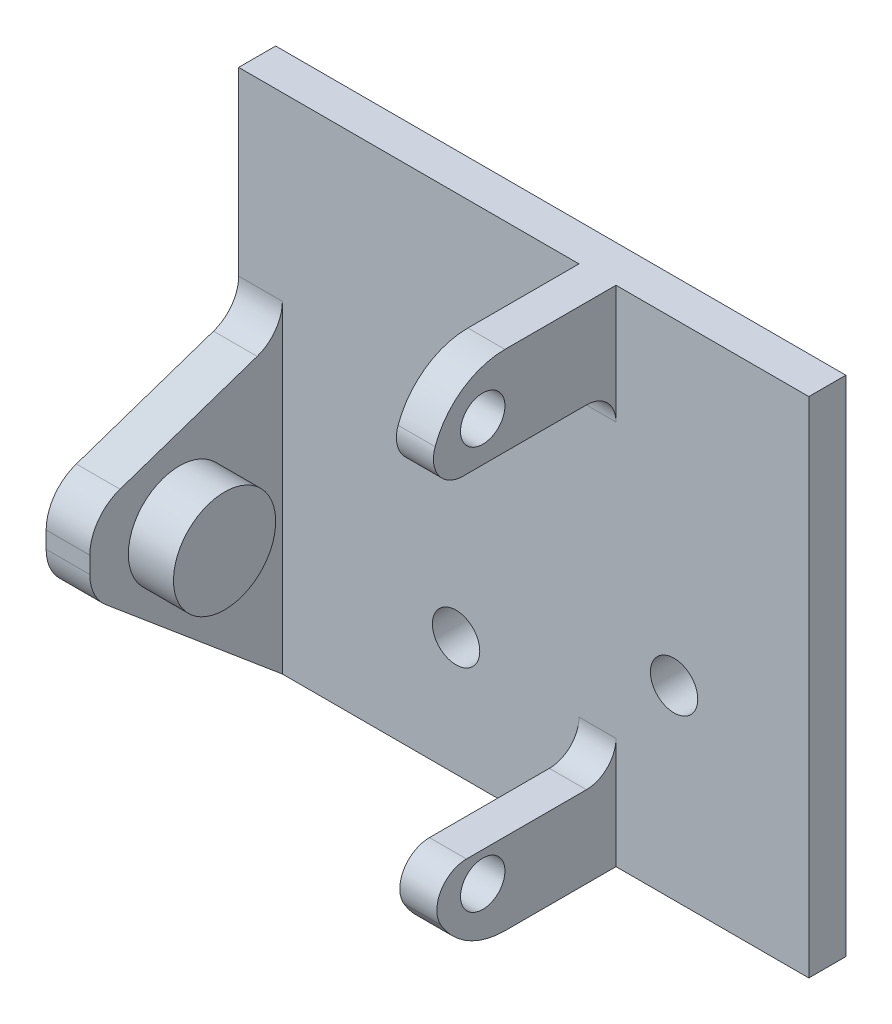
SolidWorks part; units mm, degrees
ref_plane "Plano frontal" through (0, 0, 0) normal (0, 0, 1) x (1, 0, 0)
ref_plane "Plano superior" through (0, 0, 0) normal (0, 1, 0) x (1, 0, 0)
ref_plane "Plano direito" through (0, 0, 0) normal (1, 0, 0) x (0, 0, -1)
sketch "Esboço1" plane through (0, 0, 0) normal (0, 0, 1) x (1, 0, 0)
  line L1 (-22.645, 6.7101) -> (15.855, 6.7101)
  line L2 (-22.645, 6.7101) -> (-22.645, -27.2899)
  line L3 (-22.645, -27.2899) -> (15.855, -27.2899)
  line L4 (15.855, 6.7101) -> (15.855, -27.2899)
  dimension "D1" = 38.5
  dimension "D2" = 34
extrude "Ressalto-extrusão1" add sketch "Esboço1" along normal blind 2.5
sketch "Esboço2" plane through (0, 0, 2.5) normal (0, 0, 1) x (1, 0, 0)
  line L0 (1.585, 6.7101) -> (1.585, -27.2899) construction
  line L1 (15.855, 6.7101) -> (-22.645, 6.7101) construction
  line L3 (0.335, 6.7101) -> (0.335, 0.7101)
  line L4 (0.335, 0.7101) -> (2.835, 0.7101)
  line L5 (2.835, 6.7101) -> (2.835, 0.7101)
  line L6 (0.335, 6.7101) -> (2.835, 6.7101)
  line L7 (-22.645, -21.7899) -> (15.855, -21.7899) construction
  line L8 (-22.645, 6.7101) -> (-22.645, -27.2899) construction
  line L9 (15.855, -27.2899) -> (15.855, 6.7101) construction
  line L28 (0.335, 6.7101) -> (0.335, -27.2899) construction
  line L29 (-22.645, -27.2899) -> (15.855, -27.2899) construction
  line L30 (2.835, 6.7101) -> (2.835, -27.2899) construction
  line L31 (0.335, -27.2899) -> (0.335, -21.7899)
  line L32 (0.335, -21.7899) -> (2.835, -21.7899)
  line L33 (2.835, -21.7899) -> (2.835, -27.2899)
  line L34 (2.835, -27.2899) -> (0.335, -27.2899)
  point P11 (1.585, 0.7101)
  dimension "D1" = 1.25
  dimension "D2" = 22.5
  dimension "D3" = 6
  dimension "D4" = 24.23
  dimension "D5" = 14.27
extrude "Ressalto-extrusão2" add sketch "Esboço2" along normal blind 12.5
sketch "Esboço3" plane through (2.835, 0, 0) normal (1, 0, 0) x (0, 0, -1)
  line L0 (-11.5, 6.7101) -> (-11.5, 0.7101) construction
  line L1 (-15, 6.7101) -> (-2.5, 6.7101) construction
  line L2 (-15, 0.7101) -> (-2.5, 0.7101) construction
  line L3 (-2.5, 0.7101) -> (-2.5, 6.7101) construction
  line L4 (-11.5, 6.7101) -> (-11.5, -27.2899) construction
  line L5 (-15, -21.7899) -> (-2.5, -21.7899) construction
  circle A0 centre (-11.5, 3.4101) radius 1.5
  circle A1 centre (-11.5, -23.7899) radius 1.5
  point P10 (-11.5, 1.9101)
  point P16 (-11.5, -25.2899)
  point P17 (-11.5, -22.2899)
  dimension "D2" = 1.2
  dimension "D3" = 2
  dimension "D1" = 9
extrude "Corte-extrusão1" cut sketch "Esboço3" against normal up to next
sketch "Esboço4" plane through (0, 0, 2.5) normal (0, 0, 1) x (1, 0, 0)
  line L0 (-19.695, 6.7101) -> (-19.695, -27.2899) construction
  line L1 (0.335, 6.7101) -> (-22.645, 6.7101) construction
  line L2 (-22.645, -27.2899) -> (0.335, -27.2899) construction
  line L3 (-22.645, 6.7101) -> (-22.645, -27.2899) construction
  line L4 (-19.695, -27.2899) -> (-19.695, -7.2899)
  line L5 (-19.695, -7.2899) -> (-22.645, -7.2899)
  line L6 (-22.645, -7.2899) -> (-22.645, -27.2899)
  line L7 (-22.645, -27.2899) -> (-19.695, -27.2899)
  point P6 (-19.695, -7.2899)
  dimension "D1" = 2.95
  dimension "D2" = 20
extrude "Ressalto-extrusão3" add sketch "Esboço4" along normal blind 13
sketch "Esboço5" plane through (-22.645, 0, 0) normal (-1, 0, 0) x (0, 0, 1)
  line L0 (2.5, -7.2899) -> (2.5, -27.2899) construction
  line L1 (2.5, -15.0899) -> (15.5, -15.0899) construction
  line L2 (15.5, -7.2899) -> (15.5, -27.2899) construction
  line L3 (15.5, -27.2899) -> (0, -27.2899) construction
  line L4 (2.5, -27.2899) -> (15.5, -16.3664)
  line L6 (15.5, -11.6895) -> (2.5, -7.2899)
  line L7 (15.222, -11.5954) -> (15.222, -16.5999)
  circle A0 centre (9.45, -15.0899) radius 3.45
  line M3 (0, -27.2899) -> (15.5, -27.2899)
  line M4 (15.5, -27.2899) -> (15.5, -7.2899)
  line M5 (15.5, -7.2899) -> (2.5, -7.2899)
  dimension "D2" = 6.95
  dimension "D1" = 12.2
extrude "Corte-extrusão2" cut sketch "Esboço5" against normal blind 15 contours L6 M4 M5 | L4 M3 M4 | A0 region at (-22.645, -23.6487, 11.1667) region at (-22.645, -8.7564, 11.1667) region at (-22.645, -15.0899, 9.45)
fillet "Filete1" radius 3 2 edges at (-21.17, -16.3664, 15.5) (-21.17, -11.6895, 15.5)
fillet "Filete2" radius 2.5 1 edges at (-21.17, -7.2899, 2.5)
sketch "Esboço6" plane through (-19.695, 0, 0) normal (1, 0, 0) x (0, 0, -1)
  circle A0 centre (-9.45, -15.0899) radius 3.45
sketch "Esboço7" plane through (-22.645, 0, 0) normal (-1, 0, 0) x (0, 0, 1)
  circle A0 centre (9.45, -15.0899) radius 3.45
extrude "Ressalto-extrusão5" add sketch "Esboço7" against normal blind 6
sketch "Esboço8" plane through (0, 0, 0) normal (0, 0, -1) x (-1, 0, 0)
  line L0 (7.965, 6.7101) -> (7.965, -27.2899) construction
  line L1 (-15.855, 6.7101) -> (22.645, 6.7101) construction
  line L2 (22.645, -27.2899) -> (-15.855, -27.2899) construction
  line L3 (22.645, 6.7101) -> (22.645, -27.2899) construction
  line L4 (7.965, -19.2899) -> (22.645, -19.2899) construction
  line L6 (-6.755, 6.7101) -> (-6.755, -27.2899) construction
  line L7 (-15.855, -27.2899) -> (-15.855, 6.7101) construction
  line L8 (-15.855, -14.7399) -> (-6.755, -14.7399) construction
  circle A1 centre (7.965, -19.2899) radius 1.6
  circle A2 centre (-6.755, -14.7399) radius 1.6
  dimension "D3" = 3.2
  dimension "D4" = 9.1
  dimension "D6" = 3.2
  dimension "D1" = 14.68
  dimension "D2" = 8
  dimension "D5" = 12.55
extrude "Corte-extrusão3" cut sketch "Esboço8" against normal blind 6
fillet "Filete3" radius 2 2 edges at (1.585, -21.7899, 2.5) (1.585, 0.7101, 2.5)
fillet "Filete4" radius 5 2 edges at (1.585, -27.2899, 15) (1.585, 6.7101, 15)
fillet "Filete5" radius 2 2 edges at (1.585, 0.7101, 15) (1.585, -21.7899, 15)
